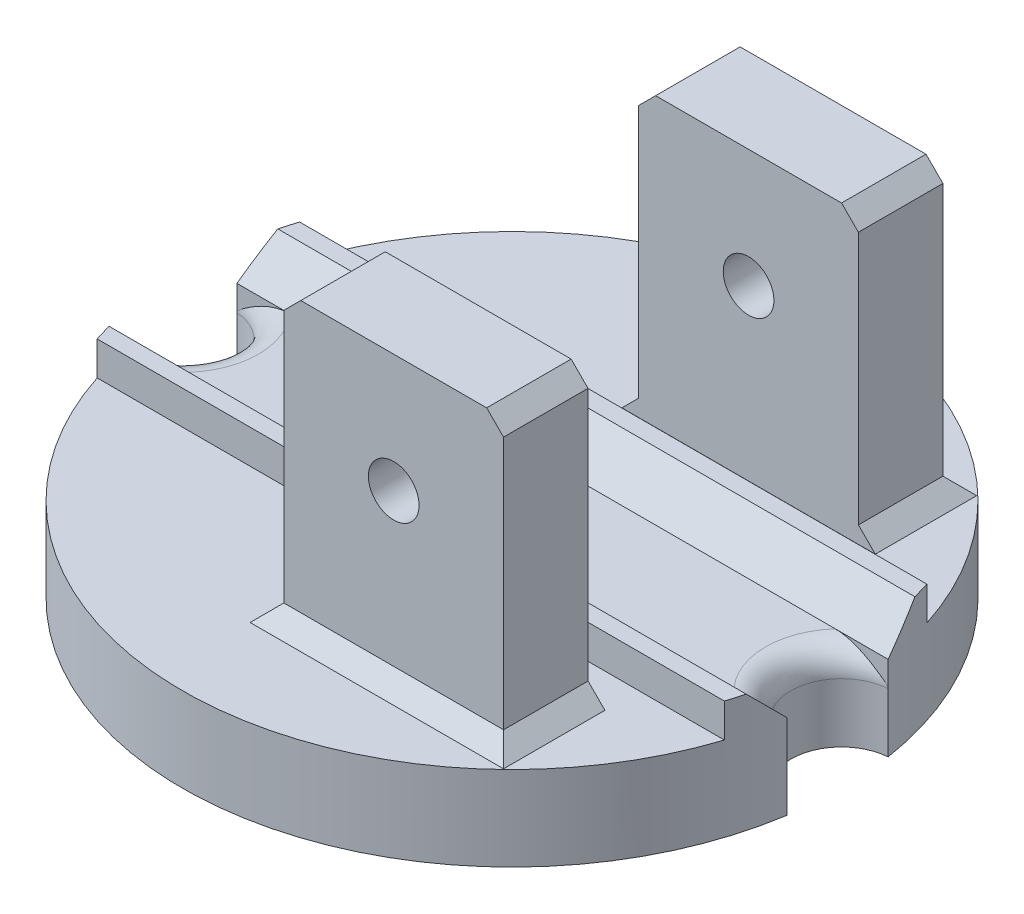
SolidWorks part; units mm, degrees
ref_plane "Front Plane" through (0, 0, 0) normal (0, 0, 1) x (1, 0, 0)
ref_plane "Top Plane" through (0, 0, 0) normal (0, 1, 0) x (1, 0, 0)
ref_plane "Right Plane" through (0, 0, 0) normal (1, 0, 0) x (0, 0, -1)
sketch "Sketch1" plane through (0, 0, 0) normal (0, 1, 0) x (1, 0, 0)
  line L0 (-24.765, 0) -> (24.765, 0) construction
  circle A0 centre (0, 0) radius 24.765 construction
  arc A1 (-24.4719, 3.7987) -> (24.4719, 3.7987) centre (0, 0) cw
  arc A2 (-24.4719, 3.7987) -> (-24.4719, -3.7987) centre (-24.765, 0) cw
  arc A3 (24.4719, 3.7987) -> (24.4719, -3.7987) centre (24.765, 0) ccw
  arc A4 (-24.4719, -3.7987) -> (24.4719, -3.7987) centre (0, 0) ccw
  dimension "D1" = 49.53
  dimension "D2" = 3.81
extrude "plate" add sketch "Sketch1" along normal blind 6.35 contours A2 A4 A3 A1 region at (0, 0, 0)
sketch "Sketch2" plane through (0, 6.35, 0) normal (0, 1, 0) x (1, 0, 0)
  line L0 (7.62, -10.16) -> (7.62, 10.16) construction
  line L1 (-0.635, 10.16) -> (15.875, 10.16)
  line L2 (-0.635, 10.16) -> (-0.635, 16.51)
  line L3 (-0.635, 16.51) -> (15.875, 16.51)
  line L4 (15.875, 16.51) -> (15.875, 10.16)
  line L5 (-20.955, 0) -> (20.955, 0) construction
  line L6 (-0.635, -16.51) -> (15.875, -16.51)
  line L7 (-0.635, -10.16) -> (-0.635, -16.51)
  line L8 (-0.635, -10.16) -> (15.875, -10.16)
  line L9 (15.875, -16.51) -> (15.875, -10.16)
  arc A0 (-24.4719, -3.7987) -> (-24.4719, 3.7987) centre (-24.765, 0) ccw construction
  arc A1 (24.4719, 3.7987) -> (24.4719, -3.7987) centre (24.765, 0) ccw construction
  point P6 (7.62, 10.16)
  point P17 (0, 0)
  dimension "D1" = 16.51
  dimension "D2" = 6.35
  dimension "D3" = 20.32
  dimension "D4" = 33.02
  dimension "D5" = 7.62
  dimension "D6" = 0.635
extrude "hook_uprights" add sketch "Sketch2" along normal blind 21.59
sketch "Sketch3" plane through (0, 0, -16.51) normal (0, 0, -1) x (-1, 0, 0)
  line L0 (-15.875, 19.05) -> (0.635, 19.05) construction
  line L1 (-15.875, 27.94) -> (-15.875, 6.35) construction
  line L2 (0.635, 27.94) -> (0.635, 6.35) construction
  line L3 (-15.875, 27.94) -> (0.635, 27.94) construction
  line L4 (24.4719, 6.35) -> (-24.4719, 6.35) construction
  circle A0 centre (-7.62, 19.05) radius 1.905
  point P10 (-8.89, 24.13)
  point P13 (-7.62, 19.05)
  dimension "D2" = 3.81
  dimension "D1" = 8.89
  dimension "D3" = 12.7
extrude "hook_bolthole" cut sketch "Sketch3" against normal through all
sketch "Sketch4" plane through (0, 6.35, 0) normal (0, 1, 0) x (1, 0, 0)
  line L0 (-24.4719, 3.7987) -> (24.4719, 3.7987)
  line L1 (24.4719, -3.7987) -> (-24.4719, -3.7987)
  line L2 (-23.5672, 7.6087) -> (23.5672, 7.6087)
  line L3 (-23.5672, -7.6087) -> (23.5672, -7.6087)
  arc A0 (-24.4719, 3.7987) -> (-23.5672, 7.6087) centre (0, 0) cw
  arc A1 (24.4719, 3.7987) -> (-24.4719, 3.7987) centre (0, 0) ccw construction
  arc A2 (23.5672, 7.6087) -> (24.4719, 3.7987) centre (0, 0) cw
  arc A3 (-24.4719, -3.7987) -> (-23.5672, -7.6087) centre (0, 0) ccw
  arc A4 (24.4719, -3.7987) -> (23.5672, -7.6087) centre (0, 0) cw
  arc A5 (-24.4719, -3.7987) -> (24.4719, -3.7987) centre (0, 0) ccw construction
  arc M9 (24.4719, 3.7987) -> (-24.4719, 3.7987) centre (0, 0) ccw
  dimension "D1" = 3.81
  dimension "D2" = 3.81
extrude "band_groove" add sketch "Sketch4" along normal blind 2.54 contours L2 L0 M9 | L3 A4 L1 A3 region at (0, 6.35, -5.6918)
fillet "Fillet4" radius 1.905 2 edges at (20.955, 6.35, 0) (-20.955, 6.35, 0)
chamfer "Chamfer1" distance 1.27 angle 45 10 edges at (15.875, 6.35, 13.335) (7.62, 6.35, 16.51) (-0.635, 6.35, 13.335) (15.875, 27.94, 13.335) (-0.635, 27.94, 13.335) (15.875, 6.35, -13.335) (7.62, 6.35, -16.51) (-0.635, 6.35, -13.335) (15.875, 27.94, -13.335) (-0.635, 27.94, -13.335)
chamfer "Chamfer2" distance 2.54 angle 45 2 edges at (0, 8.89, 3.7987) (0, 8.89, -3.7987)
